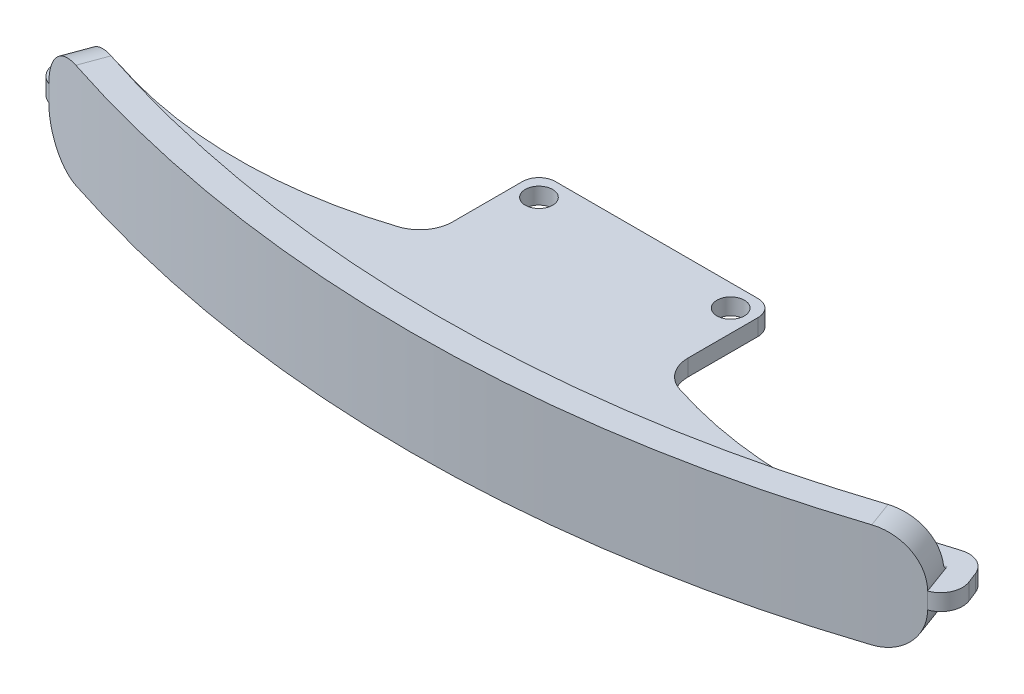
SolidWorks part; units mm, degrees
ref_plane "Front Plane" through (0, 0, 0) normal (0, 0, 1) x (1, 0, 0)
ref_plane "Top Plane" through (0, 0, 0) normal (0, 1, 0) x (1, 0, 0)
ref_plane "Right Plane" through (0, 0, 0) normal (1, 0, 0) x (0, 0, -1)
sketch "Sketch1" plane through (0, 0, 0) normal (0, 1, 0) x (1, 0, 0)
  line L0 (0, 0) -> (0, -20)
  line L1 (-62.5, -29.3272) -> (-62.5, -45) construction
  line L2 (-62.5, -45) -> (105.5, -45) construction
  line L3 (105.5, -45) -> (105.5, -29.3272) construction
  line L4 (101.8939, -20) -> (43, -20) construction
  line L5 (43, -20) -> (43, 0)
  line L6 (43, 0) -> (0, 0)
  line L7 (-58.8939, -20) -> (0, -20) construction
  line L8 (-62.5, -29.3272) -> (-58.8939, -20)
  line L9 (105.5, -29.3272) -> (101.8939, -20)
  line L10 (21.5, 0) -> (21.5, -45) construction
  arc A0 (-62.5, -29.3272) -> (105.5, -29.3272) centre (21.5, 187.9394) ccw
  arc A1 (-58.8939, -20) -> (101.8939, -20) centre (21.5, 187.9394) ccw construction
  arc A2 (-58.8939, -20) -> (0, -20) centre (-29.447, 56.1647) ccw
  arc A4 (43, -20) -> (101.8939, -20) centre (72.447, 56.1647) ccw
  point P10 (21.5, -45)
  point P17 (0, 0)
  dimension "D1" = 20
  dimension "D2" = 25
  dimension "D3" = 43
  dimension "D4" = 62.5
  dimension "D5" = 62.5
  dimension "D6" = 10
extrude "Boss-Extrude1" add sketch "Sketch1" along normal blind 3 contours L5 L6 L0 A2 L8 A0 L9 A4
sketch "Sketch3" plane through (0, 3, 0) normal (0, 1, 0) x (1, 0, 0)
  line L0 (43, 0) -> (0, 0) construction
  line L1 (0, 0) -> (0, -20) construction
  line L2 (43, -20) -> (43, 0) construction
  circle A0 centre (4, -4) radius 2.5
  circle A1 centre (39, -4) radius 2.5
  dimension "D1" = 5
  dimension "D6" = 5
  dimension "D2" = 4
  dimension "D3" = 4
  dimension "D4" = 4
  dimension "D5" = 4
extrude "Cut-Extrude2" cut sketch "Sketch3" against normal blind 3
fillet "Verrundung1" radius 4 4 edges at (105.5, 1.5, 29.3272) (101.8939, 1.5, 20) (-58.8939, 1.5, 20) (-62.5, 1.5, 29.3272)
fillet "Verrundung2" radius 6 2 edges at (43, 1.5, 20) (0, 1.5, 20)
fillet "Verrundung3" radius 3 2 edges at (0, 1.5, 0) (43, 1.5, 0)
sketch "Skizze1" plane through (0, 3, 0) normal (0, 1, 0) x (1, 0, 0)
  line L0 (-58.6911, -30.7616) -> (101.6911, -30.7616) construction
  line L1 (21.5, 0) -> (21.5, -45) construction
  line L2 (40, 0) -> (3, 0) construction
  line L3 (-58.6911, -30.7616) -> (-56.9698, -26.0673)
  line L4 (99.9698, -26.0673) -> (101.6911, -30.7616)
  arc A0 (-58.6911, -30.7616) -> (101.6911, -30.7616) centre (21.5, 187.9394) ccw construction
  arc A1 (-58.6911, -30.7616) -> (101.6911, -30.7616) centre (21.5, 187.9394) ccw
  arc A2 (-56.9698, -26.0673) -> (99.9698, -26.0673) centre (21.5, 187.9394) ccw
  dimension "D1" = 5
extrude "Aufsatz-Linear austragen1" add sketch "Skizze1" against normal blind 11 and the other way blind 8
fillet "Verrundung4" radius 8 4 edges at (100.8305, -8, 28.4145) (100.8305, 11, 28.4145) (-57.8305, 11, 28.4145) (-57.8305, -8, 28.4145)
fillet "Verrundung5" radius 1 2 edges at (21.5, 0, 40) (21.5, 3, 40)
